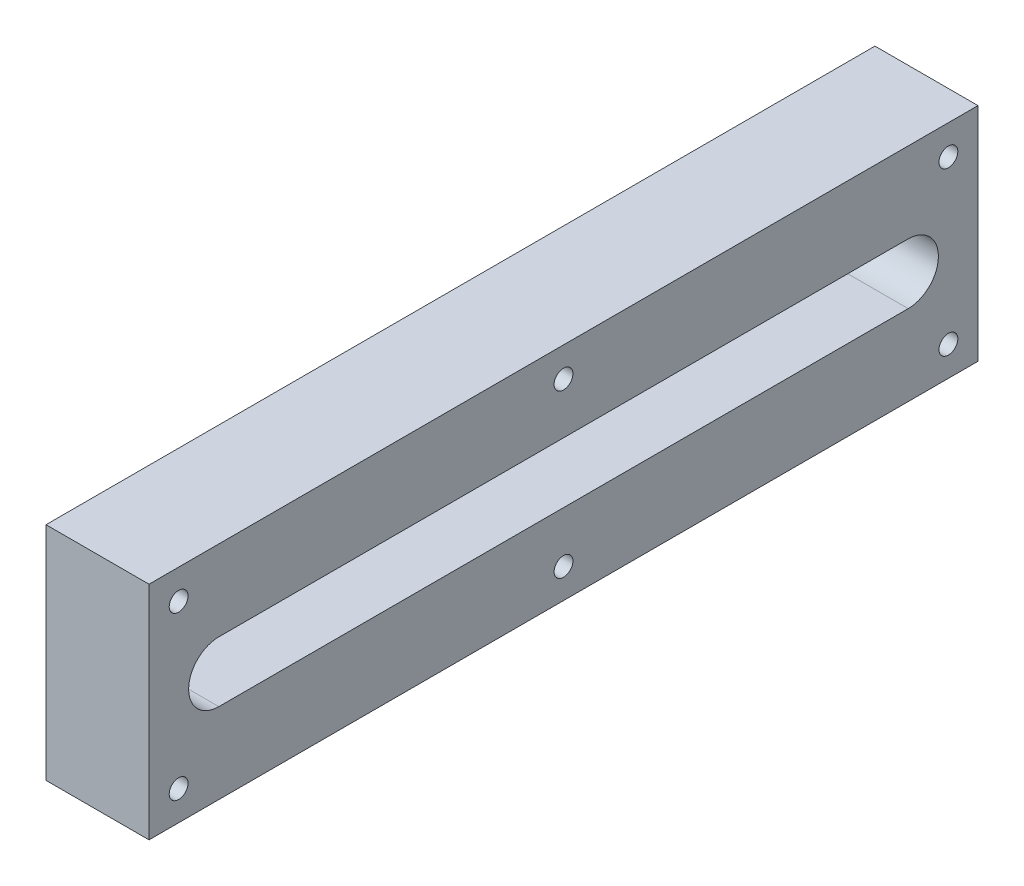
SolidWorks part; units mm, degrees
material "Delrin 2700 NC010, Low Viscosity Acetal Copolymer (SS)"
ref_plane "Front" through (0, 0, 0) normal (0, 0, 1) x (1, 0, 0)
ref_plane "Top" through (0, 0, 0) normal (0, 1, 0) x (1, 0, 0)
ref_plane "Right" through (0, 0, 0) normal (1, 0, 0) x (0, 0, -1)
sketch "Sketch1" plane through (0, 0, 0) normal (1, 0, 0) x (0, 0, -1)
  line L0 (-73.9253, 0) -> (73.9253, 0) construction
  line L1 (88.9, -23.749) -> (-88.9, -23.749)
  line L2 (88.9, -23.749) -> (88.9, 23.749)
  line L3 (88.9, 23.749) -> (-88.9, 23.749)
  line L4 (-88.9, -23.749) -> (-88.9, 23.749)
  line L5 (88.9, -23.749) -> (-88.9, 23.749) construction
  line L6 (88.9, 23.749) -> (-88.9, -23.749) construction
  line L7 (-73.9253, 2.5527) -> (73.9253, 2.5527)
  line L8 (-73.9253, -2.5527) -> (73.9253, -2.5527)
  arc A0 (-73.9253, 2.5527) -> (-73.9253, -2.5527) centre (-73.9253, 0) ccw
  arc A1 (73.9253, -2.5527) -> (73.9253, 2.5527) centre (73.9253, 0) ccw
  point P0 (0, 0)
  point P8 (0, 0)
  dimension "D4" = 5.1054
  dimension "D1" = 147.8505
  dimension "D2" = 177.8
  dimension "D3" = 47.498
extrude "Boss-Extrude1" add sketch "Sketch1" along normal blind 22.098
sketch "Sketch2" plane through (22.098, 0, 0) normal (1, 0, 0) x (0, 0, -1)
  line L0 (-73.9253, 0) -> (73.9253, 0) construction
  line L1 (-73.9253, 6.4798) -> (73.9253, 6.4798)
  line L2 (-73.9253, -6.4798) -> (73.9253, -6.4798)
  line L3 (73.9253, 2.5527) -> (-73.9253, 2.5527) construction
  arc A0 (-73.9253, 6.4798) -> (-73.9253, -6.4798) centre (-73.9253, 0) ccw
  arc A1 (73.9253, -6.4798) -> (73.9253, 6.4798) centre (73.9253, 0) ccw
  point P2 (0, 0)
  dimension "D2" = 12.9595
extrude "Cut-Extrude1" cut sketch "Sketch2" against normal offset from surface (18.249 mm away) 3.849 up to face at (0, 0, 0)
hole_wizard "#10-32 Tapped Hole1" positions "Sketch3" profile "Sketch4" tap size "#10-32" standard "ANSI Inch" end condition through all
sketch "Sketch3" plane through (22.098, 0, 0) normal (1, 0, 0) x (0, 0, -1)
  line L0 (-82.55, 17.399) -> (0, 17.399) construction
  line L1 (0, 17.399) -> (82.55, 17.399) construction
  line L3 (-82.55, 23.749) -> (-82.55, 17.399) construction
  line L4 (88.9, 23.749) -> (-88.9, 23.749) construction
  line L5 (-82.55, 17.399) -> (-82.55, -17.399) construction
  line L6 (-82.55, -17.399) -> (-82.55, -23.749) construction
  line L7 (-88.9, -23.749) -> (88.9, -23.749) construction
  line L8 (-88.9, 23.749) -> (-88.9, -23.749) construction
  point P0 (-82.55, 17.399)
  point P2 (-82.55, -17.399)
  point P4 (0, -17.399)
  point P6 (82.55, -17.399)
  point P8 (82.55, 17.399)
  point P10 (0, 17.399)
  dimension "D1" = 6.35
  dimension "D2" = 6.35
sketch "Sketch4" plane through (22.098, 17.399, 82.55) normal (0, 1, 0) x (0, 0, -1)
  line L0 (0, 0) -> (0, 22.098)
  line L1 (0, 22.098) -> (2.0193, 22.098)
  line L2 (2.0193, 22.098) -> (2.0193, 0)
  line L5 (2.0193, 0) -> (0, 0)
  line L11 (0, -6.35) -> (0, 107.95) construction
  dimension "Thru Tap Drill Dia." = 4.0386
  dimension "Thru Tap Drill Depth" = 22.098
cosmetic thread "Hole Thread1" parameters "D2"=4.826
cosmetic thread "Hole Thread2" parameters "D2"=4.826
cosmetic thread "Hole Thread3" parameters "D2"=4.826
cosmetic thread "Hole Thread4" parameters "D2"=4.826
cosmetic thread "Hole Thread5" parameters "D2"=4.826
cosmetic thread "Hole Thread6" parameters "D2"=4.826
